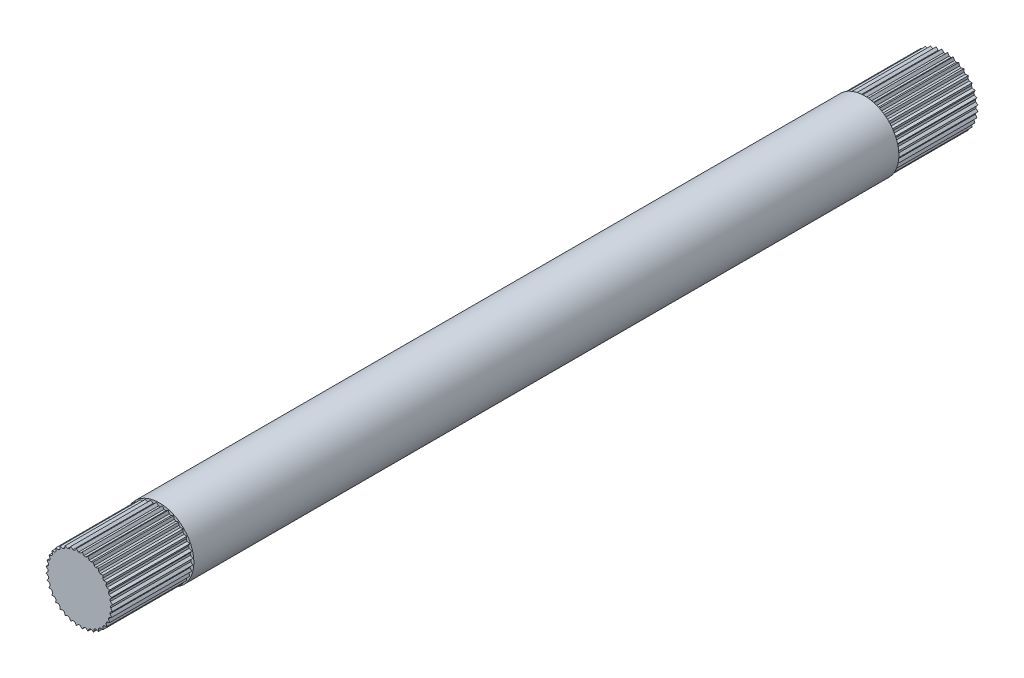
SolidWorks part; units mm, degrees
material "AISI 1015 Steel, Cold Drawn (SS)"
ref_plane "X-Y Datum" through (0, 0, 0) normal (0, 0, 1) x (1, 0, 0)
ref_plane "X-Z Datum" through (0, 0, 0) normal (0, 1, 0) x (1, 0, 0)
ref_plane "Y-Z Datum" through (0, 0, 0) normal (1, 0, 0) x (0, 0, -1)
sketch "Sketch9" plane through (0, 0, 0) normal (0, 1, 0) x (1, 0, 0)
  line L0 (16.002, 0) -> (0, 0)
  line L1 (0, 0) -> (0, -389.0916)
  line L2 (0, -389.0916) -> (-72.2493, -524.9728)
  dimension "D1" = 153.895
  dimension "D2" = 28
  dimension "D3" = 389.0916
  dimension "D5" = 16.002
sketch "Sketch5" plane through (0, 0, 0) normal (0, 1, 0) x (1, 0, 0)
  line L0 (7.9375, -262.0916) -> (7.9375, -22.1615)
  line L1 (7.9375, -22.1615) -> (9.525, -22.1615)
  line L2 (9.525, -22.1615) -> (9.525, -262.0916)
  line L3 (9.525, -262.0916) -> (7.9375, -262.0916)
  line L5 (16.002, 0) -> (0, 0) construction
  line L6 (0, 0) -> (0, -389.0916) construction
  line L7 (0, -389.0916) -> (9.525, -389.0916) construction
  line L8 (12.5602, -369.8416) -> (0, -369.8416) construction
  dimension "D1" = 1.5875
  dimension "D2" = 22.1615
  dimension "D3" = 7.9375
  dimension "D4" = 19.25
  dimension "D5" = 127
revolve "Revolve2" add sketch "Sketch5" angle 360 about L1
sketch "Sketch6" plane through (0, 0, 0) normal (0, 1, 0) x (1, 0, 0)
  circle A0 centre (0, -33.1635) radius 1.5875 construction
  circle A1 centre (0, -33.1635) radius 1.5875
sketch "Sketch7" plane through (0, 0, 0) normal (1, 0, 0) x (0, 0, -1)
  circle A2 centre (-39.196, 0) radius 1.5875
  circle A4 centre (-39.196, 0) radius 1.5875 construction
extrude "Cut-Extrude5" [suppressed] cut sketch "Sketch7" against normal through all both and the other way through all
extrude "Cut-Extrude6" [suppressed] cut sketch "Sketch6" against normal through all both and the other way through all
sketch "Sketch8" plane through (0, 0, 0) normal (0, 0, 1) x (1, 0, 0)
  line L0 (9.2357, -0.808) -> (8.6817, -0.254)
  line L1 (8.6817, -0.254) -> (8.6817, 0.254)
  line L2 (8.6817, 0.254) -> (9.2357, 0.808)
  line L3 (8.6817, 0) -> (0, 0) construction
  line L4 (8.9551, -2.3995) -> (8.5057, -1.7577)
  line L5 (8.5057, -1.7577) -> (8.5939, -1.2574)
  line L6 (8.5939, -1.2574) -> (9.2357, -0.808)
  line L7 (8.4024, -3.9181) -> (8.0713, -3.208)
  line L8 (8.0713, -3.208) -> (8.245, -2.7306)
  line L9 (8.245, -2.7306) -> (8.9551, -2.3995)
  line L10 (7.5944, -5.3176) -> (7.3916, -4.5608)
  line L11 (7.3916, -4.5608) -> (7.6456, -4.1209)
  line L12 (7.6456, -4.1209) -> (8.4024, -3.9181)
  line L13 (6.5556, -6.5556) -> (6.4873, -5.7751)
  line L14 (6.4873, -5.7751) -> (6.8138, -5.3859)
  line L15 (6.8138, -5.3859) -> (7.5944, -5.3176)
  line L16 (5.3176, -7.5944) -> (5.3859, -6.8138)
  line L17 (5.3859, -6.8138) -> (5.7751, -6.4873)
  line L18 (5.7751, -6.4873) -> (6.5556, -6.5556)
  line L19 (3.9181, -8.4024) -> (4.1209, -7.6456)
  line L20 (4.1209, -7.6456) -> (4.5608, -7.3916)
  line L21 (4.5608, -7.3916) -> (5.3176, -7.5944)
  line L22 (2.3995, -8.9551) -> (2.7306, -8.245)
  line L23 (2.7306, -8.245) -> (3.208, -8.0713)
  line L24 (3.208, -8.0713) -> (3.9181, -8.4024)
  line L25 (0.808, -9.2357) -> (1.2574, -8.5939)
  line L26 (1.2574, -8.5939) -> (1.7577, -8.5057)
  line L27 (1.7577, -8.5057) -> (2.3995, -8.9551)
  line L28 (-0.808, -9.2357) -> (-0.254, -8.6817)
  line L29 (-0.254, -8.6817) -> (0.254, -8.6817)
  line L30 (0.254, -8.6817) -> (0.808, -9.2357)
  line L31 (-2.3995, -8.9551) -> (-1.7577, -8.5057)
  line L32 (-1.7577, -8.5057) -> (-1.2574, -8.5939)
  line L33 (-1.2574, -8.5939) -> (-0.808, -9.2357)
  line L34 (-3.9181, -8.4024) -> (-3.208, -8.0713)
  line L35 (-3.208, -8.0713) -> (-2.7306, -8.245)
  line L36 (-2.7306, -8.245) -> (-2.3995, -8.9551)
  line L37 (-5.3176, -7.5944) -> (-4.5608, -7.3916)
  line L38 (-4.5608, -7.3916) -> (-4.1209, -7.6456)
  line L39 (-4.1209, -7.6456) -> (-3.9181, -8.4024)
  line L40 (-6.5556, -6.5556) -> (-5.7751, -6.4873)
  line L41 (-5.7751, -6.4873) -> (-5.3859, -6.8138)
  line L42 (-5.3859, -6.8138) -> (-5.3176, -7.5944)
  line L43 (-7.5944, -5.3176) -> (-6.8138, -5.3859)
  line L44 (-6.8138, -5.3859) -> (-6.4873, -5.7751)
  line L45 (-6.4873, -5.7751) -> (-6.5556, -6.5556)
  line L46 (-8.4024, -3.9181) -> (-7.6456, -4.1209)
  line L47 (-7.6456, -4.1209) -> (-7.3916, -4.5608)
  line L48 (-7.3916, -4.5608) -> (-7.5944, -5.3176)
  line L49 (-8.9551, -2.3995) -> (-8.245, -2.7306)
  line L50 (-8.245, -2.7306) -> (-8.0713, -3.208)
  line L51 (-8.0713, -3.208) -> (-8.4024, -3.9181)
  line L52 (-9.2357, -0.808) -> (-8.5939, -1.2574)
  line L53 (-8.5939, -1.2574) -> (-8.5057, -1.7577)
  line L54 (-8.5057, -1.7577) -> (-8.9551, -2.3995)
  line L55 (-9.2357, 0.808) -> (-8.6817, 0.254)
  line L56 (-8.6817, 0.254) -> (-8.6817, -0.254)
  line L57 (-8.6817, -0.254) -> (-9.2357, -0.808)
  line L58 (-8.9551, 2.3995) -> (-8.5057, 1.7577)
  line L59 (-8.5057, 1.7577) -> (-8.5939, 1.2574)
  line L60 (-8.5939, 1.2574) -> (-9.2357, 0.808)
  line L61 (-8.4024, 3.9181) -> (-8.0713, 3.208)
  line L62 (-8.0713, 3.208) -> (-8.245, 2.7306)
  line L63 (-8.245, 2.7306) -> (-8.9551, 2.3995)
  line L64 (-7.5944, 5.3176) -> (-7.3916, 4.5608)
  line L65 (-7.3916, 4.5608) -> (-7.6456, 4.1209)
  line L66 (-7.6456, 4.1209) -> (-8.4024, 3.9181)
  line L67 (-6.5556, 6.5556) -> (-6.4873, 5.7751)
  line L68 (-6.4873, 5.7751) -> (-6.8138, 5.3859)
  line L69 (-6.8138, 5.3859) -> (-7.5944, 5.3176)
  line L70 (-5.3176, 7.5944) -> (-5.3859, 6.8138)
  line L71 (-5.3859, 6.8138) -> (-5.7751, 6.4873)
  line L72 (-5.7751, 6.4873) -> (-6.5556, 6.5556)
  line L73 (-3.9181, 8.4024) -> (-4.1209, 7.6456)
  line L74 (-4.1209, 7.6456) -> (-4.5608, 7.3916)
  line L75 (-4.5608, 7.3916) -> (-5.3176, 7.5944)
  line L76 (-2.3995, 8.9551) -> (-2.7306, 8.245)
  line L77 (-2.7306, 8.245) -> (-3.208, 8.0713)
  line L78 (-3.208, 8.0713) -> (-3.9181, 8.4024)
  line L79 (-0.808, 9.2357) -> (-1.2574, 8.5939)
  line L80 (-1.2574, 8.5939) -> (-1.7577, 8.5057)
  line L81 (-1.7577, 8.5057) -> (-2.3995, 8.9551)
  line L82 (0.808, 9.2357) -> (0.254, 8.6817)
  line L83 (0.254, 8.6817) -> (-0.254, 8.6817)
  line L84 (-0.254, 8.6817) -> (-0.808, 9.2357)
  line L85 (2.3995, 8.9551) -> (1.7577, 8.5057)
  line L86 (1.7577, 8.5057) -> (1.2574, 8.5939)
  line L87 (1.2574, 8.5939) -> (0.808, 9.2357)
  line L88 (3.9181, 8.4024) -> (3.208, 8.0713)
  line L89 (3.208, 8.0713) -> (2.7306, 8.245)
  line L90 (2.7306, 8.245) -> (2.3995, 8.9551)
  line L91 (5.3176, 7.5944) -> (4.5608, 7.3916)
  line L92 (4.5608, 7.3916) -> (4.1209, 7.6456)
  line L93 (4.1209, 7.6456) -> (3.9181, 8.4024)
  line L94 (6.5556, 6.5556) -> (5.7751, 6.4873)
  line L95 (5.7751, 6.4873) -> (5.3859, 6.8138)
  line L96 (5.3859, 6.8138) -> (5.3176, 7.5944)
  line L97 (7.5944, 5.3176) -> (6.8138, 5.3859)
  line L98 (6.8138, 5.3859) -> (6.4873, 5.7751)
  line L99 (6.4873, 5.7751) -> (6.5556, 6.5556)
  line L100 (8.4024, 3.9181) -> (7.6456, 4.1209)
  line L101 (7.6456, 4.1209) -> (7.3916, 4.5608)
  line L102 (7.3916, 4.5608) -> (7.5944, 5.3176)
  line L103 (8.9551, 2.3995) -> (8.245, 2.7306)
  line L104 (8.245, 2.7306) -> (8.0713, 3.208)
  line L105 (8.0713, 3.208) -> (8.4024, 3.9181)
  line L106 (9.2357, 0.808) -> (8.5939, 1.2574)
  line L107 (8.5939, 1.2574) -> (8.5057, 1.7577)
  line L108 (8.5057, 1.7577) -> (8.9551, 2.3995)
  circle A0 centre (0, 0) radius 12.7
  circle A1 centre (0, 0) radius 9.271 construction
  circle A2 centre (0, 0) radius 8.6854 construction
  point P153 (0, 0)
  dimension "D1" = 25.4
  dimension "D4" = 18.542
  dimension "D6" = 17.3708
  dimension "D2" = 0.508
  dimension "D3" = 135
  dimension "D5" = 36
extrude "Cut-Extrude7" cut sketch "Sketch8" against normal blind 22.225 from surface starting at face at (-9.525, 0, 262.0916)
ref_plane "Plane1" through (0, 0, 47.5615) normal (0, 0, -1) x (-1, 0, 0)
sketch "Sketch10" plane through (0, 0, 47.5615) normal (0, 0, -1) x (-1, 0, 0)
  circle A0 centre (0, 0) radius 7.9375
  dimension "D1" = 15.875
extrude "Boss-Extrude1" add sketch "Sketch10" against normal up to surface (214.5301 mm away) up to face at (-7.9375, 0, 262.0916)
sketch "Sketch11" plane through (0, 0, 22.1615) normal (0, 0, -1) x (-1, 0, 0)
  line L0 (0, 9.525) -> (13.3548, 9.525) construction
  line L1 (0, 9.525) -> (0, 15.4312) construction
  line L2 (-9.525, 0) -> (-9.525, 9.1744) construction
  line L3 (-9.525, 0) -> (-16.674, 0) construction
  circle A0 centre (0, 0) radius 9.525 construction
  point P0 (0, 9.525)
  point P1 (-9.525, 0)
sketch "Sketch12" plane through (0, 0, 0) normal (0, 0, 1) x (1, 0, 0)
  line L0 (9.2357, -0.808) -> (8.6817, -0.254)
  line L1 (8.6817, -0.254) -> (8.6817, 0.254)
  line L2 (8.6817, 0.254) -> (9.2357, 0.808)
  line L3 (8.6817, 0) -> (0, 0) construction
  line L4 (8.9551, -2.3995) -> (8.5057, -1.7577)
  line L5 (8.5057, -1.7577) -> (8.5939, -1.2574)
  line L6 (8.5939, -1.2574) -> (9.2357, -0.808)
  line L7 (8.4024, -3.9181) -> (8.0713, -3.208)
  line L8 (8.0713, -3.208) -> (8.245, -2.7306)
  line L9 (8.245, -2.7306) -> (8.9551, -2.3995)
  line L10 (7.5944, -5.3176) -> (7.3916, -4.5608)
  line L11 (7.3916, -4.5608) -> (7.6456, -4.1209)
  line L12 (7.6456, -4.1209) -> (8.4024, -3.9181)
  line L13 (6.5556, -6.5556) -> (6.4873, -5.7751)
  line L14 (6.4873, -5.7751) -> (6.8138, -5.3859)
  line L15 (6.8138, -5.3859) -> (7.5944, -5.3176)
  line L16 (5.3176, -7.5944) -> (5.3859, -6.8138)
  line L17 (5.3859, -6.8138) -> (5.7751, -6.4873)
  line L18 (5.7751, -6.4873) -> (6.5556, -6.5556)
  line L19 (3.9181, -8.4024) -> (4.1209, -7.6456)
  line L20 (4.1209, -7.6456) -> (4.5608, -7.3916)
  line L21 (4.5608, -7.3916) -> (5.3176, -7.5944)
  line L22 (2.3995, -8.9551) -> (2.7306, -8.245)
  line L23 (2.7306, -8.245) -> (3.208, -8.0713)
  line L24 (3.208, -8.0713) -> (3.9181, -8.4024)
  line L25 (0.808, -9.2357) -> (1.2574, -8.5939)
  line L26 (1.2574, -8.5939) -> (1.7577, -8.5057)
  line L27 (1.7577, -8.5057) -> (2.3995, -8.9551)
  line L28 (-0.808, -9.2357) -> (-0.254, -8.6817)
  line L29 (-0.254, -8.6817) -> (0.254, -8.6817)
  line L30 (0.254, -8.6817) -> (0.808, -9.2357)
  line L31 (-2.3995, -8.9551) -> (-1.7577, -8.5057)
  line L32 (-1.7577, -8.5057) -> (-1.2574, -8.5939)
  line L33 (-1.2574, -8.5939) -> (-0.808, -9.2357)
  line L34 (-3.9181, -8.4024) -> (-3.208, -8.0713)
  line L35 (-3.208, -8.0713) -> (-2.7306, -8.245)
  line L36 (-2.7306, -8.245) -> (-2.3995, -8.9551)
  line L37 (-5.3176, -7.5944) -> (-4.5608, -7.3916)
  line L38 (-4.5608, -7.3916) -> (-4.1209, -7.6456)
  line L39 (-4.1209, -7.6456) -> (-3.9181, -8.4024)
  line L40 (-6.5556, -6.5556) -> (-5.7751, -6.4873)
  line L41 (-5.7751, -6.4873) -> (-5.3859, -6.8138)
  line L42 (-5.3859, -6.8138) -> (-5.3176, -7.5944)
  line L43 (-7.5944, -5.3176) -> (-6.8138, -5.3859)
  line L44 (-6.8138, -5.3859) -> (-6.4873, -5.7751)
  line L45 (-6.4873, -5.7751) -> (-6.5556, -6.5556)
  line L46 (-8.4024, -3.9181) -> (-7.6456, -4.1209)
  line L47 (-7.6456, -4.1209) -> (-7.3916, -4.5608)
  line L48 (-7.3916, -4.5608) -> (-7.5944, -5.3176)
  line L49 (-8.9551, -2.3995) -> (-8.245, -2.7306)
  line L50 (-8.245, -2.7306) -> (-8.0713, -3.208)
  line L51 (-8.0713, -3.208) -> (-8.4024, -3.9181)
  line L52 (-9.2357, -0.808) -> (-8.5939, -1.2574)
  line L53 (-8.5939, -1.2574) -> (-8.5057, -1.7577)
  line L54 (-8.5057, -1.7577) -> (-8.9551, -2.3995)
  line L55 (-9.2357, 0.808) -> (-8.6817, 0.254)
  line L56 (-8.6817, 0.254) -> (-8.6817, -0.254)
  line L57 (-8.6817, -0.254) -> (-9.2357, -0.808)
  line L58 (-8.9551, 2.3995) -> (-8.5057, 1.7577)
  line L59 (-8.5057, 1.7577) -> (-8.5939, 1.2574)
  line L60 (-8.5939, 1.2574) -> (-9.2357, 0.808)
  line L61 (-8.4024, 3.9181) -> (-8.0713, 3.208)
  line L62 (-8.0713, 3.208) -> (-8.245, 2.7306)
  line L63 (-8.245, 2.7306) -> (-8.9551, 2.3995)
  line L64 (-7.5944, 5.3176) -> (-7.3916, 4.5608)
  line L65 (-7.3916, 4.5608) -> (-7.6456, 4.1209)
  line L66 (-7.6456, 4.1209) -> (-8.4024, 3.9181)
  line L67 (-6.5556, 6.5556) -> (-6.4873, 5.7751)
  line L68 (-6.4873, 5.7751) -> (-6.8138, 5.3859)
  line L69 (-6.8138, 5.3859) -> (-7.5944, 5.3176)
  line L70 (-5.3176, 7.5944) -> (-5.3859, 6.8138)
  line L71 (-5.3859, 6.8138) -> (-5.7751, 6.4873)
  line L72 (-5.7751, 6.4873) -> (-6.5556, 6.5556)
  line L73 (-3.9181, 8.4024) -> (-4.1209, 7.6456)
  line L74 (-4.1209, 7.6456) -> (-4.5608, 7.3916)
  line L75 (-4.5608, 7.3916) -> (-5.3176, 7.5944)
  line L76 (-2.3995, 8.9551) -> (-2.7306, 8.245)
  line L77 (-2.7306, 8.245) -> (-3.208, 8.0713)
  line L78 (-3.208, 8.0713) -> (-3.9181, 8.4024)
  line L79 (-0.808, 9.2357) -> (-1.2574, 8.5939)
  line L80 (-1.2574, 8.5939) -> (-1.7577, 8.5057)
  line L81 (-1.7577, 8.5057) -> (-2.3995, 8.9551)
  line L82 (0.808, 9.2357) -> (0.254, 8.6817)
  line L83 (0.254, 8.6817) -> (-0.254, 8.6817)
  line L84 (-0.254, 8.6817) -> (-0.808, 9.2357)
  line L85 (2.3995, 8.9551) -> (1.7577, 8.5057)
  line L86 (1.7577, 8.5057) -> (1.2574, 8.5939)
  line L87 (1.2574, 8.5939) -> (0.808, 9.2357)
  line L88 (3.9181, 8.4024) -> (3.208, 8.0713)
  line L89 (3.208, 8.0713) -> (2.7306, 8.245)
  line L90 (2.7306, 8.245) -> (2.3995, 8.9551)
  line L91 (5.3176, 7.5944) -> (4.5608, 7.3916)
  line L92 (4.5608, 7.3916) -> (4.1209, 7.6456)
  line L93 (4.1209, 7.6456) -> (3.9181, 8.4024)
  line L94 (6.5556, 6.5556) -> (5.7751, 6.4873)
  line L95 (5.7751, 6.4873) -> (5.3859, 6.8138)
  line L96 (5.3859, 6.8138) -> (5.3176, 7.5944)
  line L97 (7.5944, 5.3176) -> (6.8138, 5.3859)
  line L98 (6.8138, 5.3859) -> (6.4873, 5.7751)
  line L99 (6.4873, 5.7751) -> (6.5556, 6.5556)
  line L100 (8.4024, 3.9181) -> (7.6456, 4.1209)
  line L101 (7.6456, 4.1209) -> (7.3916, 4.5608)
  line L102 (7.3916, 4.5608) -> (7.5944, 5.3176)
  line L103 (8.9551, 2.3995) -> (8.245, 2.7306)
  line L104 (8.245, 2.7306) -> (8.0713, 3.208)
  line L105 (8.0713, 3.208) -> (8.4024, 3.9181)
  line L106 (9.2357, 0.808) -> (8.5939, 1.2574)
  line L107 (8.5939, 1.2574) -> (8.5057, 1.7577)
  line L108 (8.5057, 1.7577) -> (8.9551, 2.3995)
  circle A0 centre (0, 0) radius 12.7
  circle A1 centre (0, 0) radius 9.271 construction
  circle A2 centre (0, 0) radius 8.6854 construction
  point P153 (0, 0)
  dimension "D1" = 25.4
  dimension "D4" = 18.542
  dimension "D6" = 17.3708
  dimension "D2" = 0.508
  dimension "D3" = 135
  dimension "D5" = 36
extrude "Cut-Extrude8" cut sketch "Sketch12" along normal blind 22.225 from surface starting at face at (-7.9375, 0, 22.1615)
